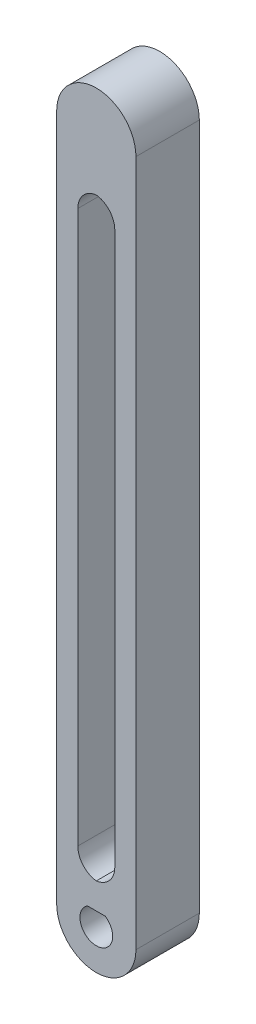
SolidWorks part; units mm, degrees
ref_plane "Front Plane" through (0, 0, 0) normal (0, 0, 1) x (1, 0, 0)
ref_plane "Top Plane" through (0, 0, 0) normal (0, 1, 0) x (1, 0, 0)
ref_plane "Right Plane" through (0, 0, 0) normal (1, 0, 0) x (0, 0, -1)
sketch "Sketch1" plane through (0, 0, 0) normal (0, 0, 1) x (1, 0, 0)
  line L0 (-5.6452, 102.5806) -> (-5.6452, -27.4194)
  line L1 (9.3548, 102.5806) -> (9.3548, -27.4194)
  arc A0 (-5.6452, 102.5806) -> (9.3548, 102.5806) centre (1.8548, 102.5806) cw
  arc A1 (-5.6452, -27.4194) -> (9.3548, -27.4194) centre (1.8548, -27.4194) ccw
  dimension "D1" = 15
  dimension "D2" = 130
extrude "Boss-Extrude1" add sketch "Sketch1" along normal blind 12
sketch "Sketch2" plane through (0, 0, 12) normal (0, 0, 1) x (1, 0, 0)
  line L0 (-5.6452, -27.4194) -> (9.3548, -27.4194) construction
  circle A0 centre (1.8548, -27.4194) radius 3.1
extrude "Boss-Extrude2" add sketch "Sketch2" along normal blind 15
sketch "Sketch3" plane through (0, 0, 27) normal (0, 0, 1) x (1, 0, 0)
  line L0 (0.1666, -24.8194) -> (3.543, -24.8194)
  circle A0 centre (1.8548, -27.4194) radius 3.1 construction
  circle A1 centre (1.8548, -27.4194) radius 3.1 construction
  arc A2 (0.1666, -24.8194) -> (3.543, -24.8194) centre (1.8548, -27.4194) ccw
  dimension "3.6" = 2.6
extrude "Cut-Extrude1" cut sketch "Sketch3" against normal blind 50
sketch "Sketch4" plane through (0, 0, 27) normal (0, 0, 1) x (1, 0, 0)
  line L0 (0.1666, -24.8194) -> (3.543, -24.8194)
  arc A0 (0.1666, -24.8194) -> (3.543, -24.8194) centre (1.8548, -27.4194) cw
extrude "Cut-Extrude2" cut sketch "Sketch4" against normal blind 15
sketch "Sketch5" plane through (0, 0, 12) normal (0, 0, 1) x (1, 0, 0)
  line L0 (-5.6452, 102.5806) -> (-5.6452, -27.4194) construction
  line L1 (-1.6452, -19.9194) -> (-5.6452, -19.9194) construction
  line L2 (-1.6452, -19.9194) -> (-1.6452, 92.5806) construction
  line L3 (-1.6452, 92.5806) -> (-5.6452, 92.5806) construction
  line L4 (-5.6452, -19.9194) -> (-5.6452, 92.5806) construction
  line L6 (5.3548, -19.9194) -> (9.3548, -19.9194) construction
  line L7 (5.3548, -19.9194) -> (5.3548, 92.5806) construction
  line L8 (5.3548, 92.5806) -> (9.3548, 92.5806) construction
  line L9 (9.3548, -19.9194) -> (9.3548, 92.5806) construction
  line L10 (-1.6452, 92.5806) -> (5.3548, 92.5806)
  line L11 (-1.6452, 92.5806) -> (-1.6452, -19.9194)
  line L12 (-1.6452, -19.9194) -> (5.3548, -19.9194)
  line L13 (5.3548, 92.5806) -> (5.3548, -19.9194)
  arc A0 (-5.6452, -27.4194) -> (9.3548, -27.4194) centre (1.8548, -27.4194) cw construction
  arc A1 (9.3548, 102.5806) -> (-5.6452, 102.5806) centre (1.8548, 102.5806) ccw construction
  dimension "D1" = 4
  dimension "D2" = 4
  dimension "D3" = 10
extrude "Cut-Extrude3" cut sketch "Sketch5" against normal blind 12
sketch "Sketch6" plane through (-5.6452, 0, 0) normal (-1, 0, 0) x (0, 0, 1)
  line L0 (6, 102.5806) -> (6, 14.8619) construction
  line L1 (12, 102.5806) -> (0, 102.5806) construction
  circle A0 centre (6, 78.769) radius 5.15
  circle A1 centre (6, 53.769) radius 5.15
  circle A2 centre (6, 28.769) radius 5.15
  dimension "D1" = 3
extrude "Cut-Extrude4" cut sketch "Sketch6" against normal blind 2
fillet "Fillet1" radius 4 4 edges at (-1.6452, -19.9194, 6) (5.3548, -19.9194, 6) (5.3548, 92.5806, 6) (-1.6452, 92.5806, 6)
